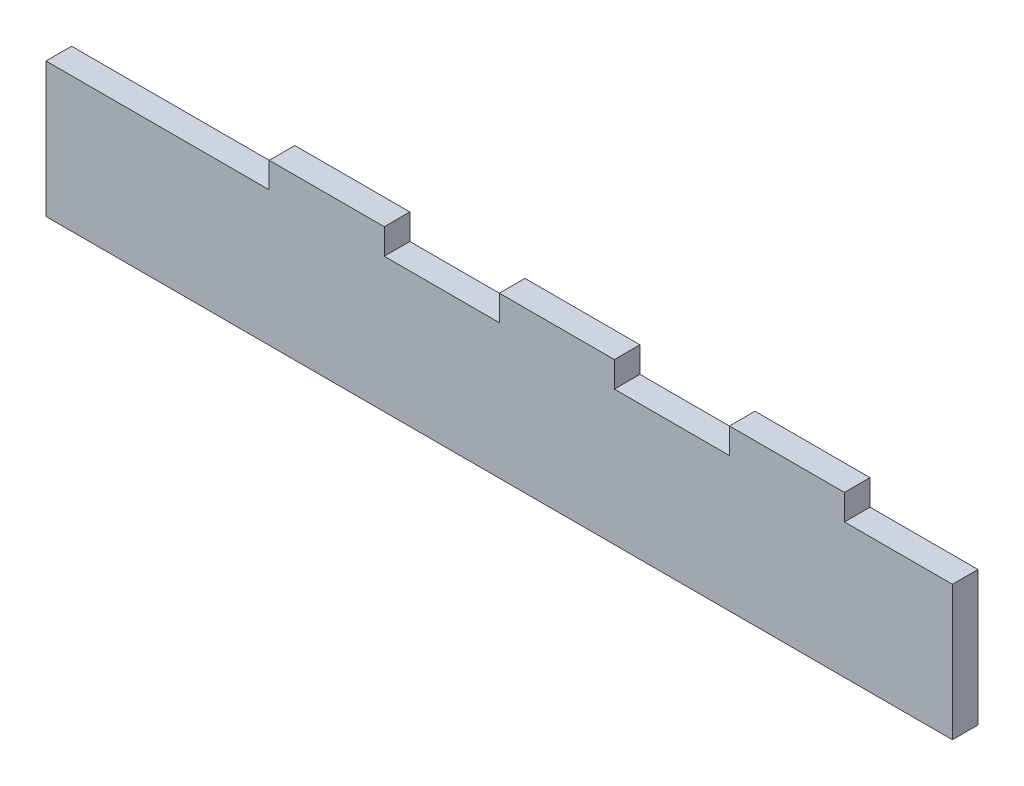
SolidWorks part; units mm, degrees
ref_plane "Front Plane" through (0, 0, 0) normal (0, 0, 1) x (1, 0, 0)
ref_plane "Top Plane" through (0, 0, 0) normal (0, 1, 0) x (1, 0, 0)
ref_plane "Right Plane" through (0, 0, 0) normal (1, 0, 0) x (0, 0, -1)
sketch "Sketch1" plane through (0, 0, 0) normal (0, 0, 1) x (1, 0, 0)
  line L1 (0, 0) -> (170.942, 0)
  line L2 (0, 0) -> (0, 30.226)
  line L3 (0, 30.226) -> (170.942, 30.226)
  line L4 (170.942, 0) -> (170.942, 30.226)
  dimension "D1" = 170.942
  dimension "D2" = 30.226
extrude "Boss-Extrude1" add sketch "Sketch1" along normal blind 4.826
sketch "Sketch2" plane through (0, 0, 0) normal (0, 0, -1) x (-1, 0, 0)
  line L0 (0, 25.4) -> (-42.0951, 25.4) construction
  line L1 (0, 25.4) -> (0, 30.226) construction
  line L2 (0, 30.226) -> (-42.0951, 30.226) construction
  line L3 (-42.0951, 30.226) -> (-42.0951, 25.4) construction
  line L4 (-63.7923, 25.4) -> (-85.4895, 25.4) construction
  line L5 (-85.4895, 30.226) -> (-85.4895, 25.4) construction
  line L6 (-63.7923, 30.226) -> (-63.7923, 25.4) construction
  line L7 (-63.7923, 30.226) -> (-85.4895, 30.226) construction
  line L8 (-107.1867, 25.4) -> (-128.8839, 25.4) construction
  line L9 (-128.8839, 30.226) -> (-128.8839, 25.4) construction
  line L10 (-107.1867, 30.226) -> (-107.1867, 25.4) construction
  line L11 (-107.1867, 30.226) -> (-128.8839, 30.226) construction
  line L12 (-150.5811, 25.4) -> (-170.979, 25.4) construction
  line L13 (-150.5811, 30.226) -> (-150.5811, 25.4) construction
  line L14 (-170.979, 25.4) -> (-170.979, 30.226) construction
  line L15 (-150.5811, 30.226) -> (-170.979, 30.226) construction
  line L16 (0, 25.4) -> (-42.0951, 25.4)
  line L17 (0, 25.4) -> (0, 30.226)
  line L18 (0, 30.226) -> (-42.0951, 30.226)
  line L19 (-42.0951, 30.226) -> (-42.0951, 25.4)
  line L20 (-63.7923, 25.4) -> (-85.4895, 25.4)
  line L21 (-85.4895, 30.226) -> (-85.4895, 25.4)
  line L22 (-63.7923, 30.226) -> (-63.7923, 25.4)
  line L23 (-63.7923, 30.226) -> (-85.4895, 30.226)
  line L24 (-107.1867, 25.4) -> (-128.8839, 25.4)
  line L25 (-128.8839, 30.226) -> (-128.8839, 25.4)
  line L26 (-107.1867, 30.226) -> (-107.1867, 25.4)
  line L27 (-107.1867, 30.226) -> (-128.8839, 30.226)
  line L28 (-150.5811, 25.4) -> (-170.979, 25.4)
  line L29 (-150.5811, 30.226) -> (-150.5811, 25.4)
  line L30 (-170.979, 25.4) -> (-170.979, 30.226)
  line L31 (-150.5811, 30.226) -> (-170.979, 30.226)
extrude "Cut-Extrude1" cut sketch "Sketch2" against normal through all
equation "\"MDF\"= 0.19in"
equation "\"PVCID\" = 2.067in"
equation "\"PVCOD\" = 2.375in"
equation "\"GenDiameter\"= 60mm"
equation "\"GenCutDiameter\" = 1.8in"
equation "\"GenCutDistance\" = 1"
equation "\"TowerHeight\" = 6in"
equation "\"TowerFrontBase\" = 3in"
equation "\"FunnelHeight\" = 1in"
equation "\"FunnelAngle\" = 20"
equation "\"TowerSideBase\" = 3in"
equation "\"TowerPanelLength\" = 2in"
equation "\"TowerPanelLeeway\" = 0.5in"
equation "\"BaseLength\" = 9in"
equation "\"BaseWidth\" = 10in"
equation "\"WheelHoleLength\" = 3.25in"
equation "\"WheelHoleWidth\" = 26mm"
equation "\"WheelHoleFromBack\" = 1.5in"
equation "\"DropLength\" = 1in"
equation "\"DropWidth\" = 8.5in"
equation "\"BumperWidth\" = 1in"
equation "\"SmallHexDiameter\" = 0.185in"
equation "\"SmallHexHeight\" = 0.701in"
equation "\"ScrewSize\" = 0.106in"
equation "\"BigHexDiameter\" = 0.251in"
equation "\"BigHexHeight\" = 0.374in"
equation "\"PCBThickness\" = 0.066in"
equation "\"ConnectorHeight\" = 0.517in"
equation "\"BoardHeight\" = 0.583in"
equation "\"UnoStackHeight\" = 1.351in"
equation "\"UnoStackWidth\" = 3.053in"
equation "\"UnoStackLength\" = 3.152in"
equation "\"HBridgeWidth\" = 1.797in"
equation "\"HBridgeLength\" = 2.236in"
equation "\"DSWidth\" = 1.820in"
equation "\"DSLength\" = 1.833in"
equation "\"StepperWidth\" = 1.799in"
equation "\"StepperLength\" = 2.248in"
equation "\"ULNWidth\" = 1.304in"
equation "\"ULNLength\" = 1.545in"
equation "\"VSwitchHeight\" = 0.392in"
equation "\"VSwitchWidth\" = 0.637in"
equation "\"VSwitchLength\" = 1.097in"
equation "\"SkateWheelDiameter\" = 80mm"
equation "\"SkateWheelThickness\" = 24mm"
equation "\"BaseDistance\" = 3in"
equation "\"DummyVar\" = 2in"
equation "\"D2@Sketch1\"=\"MDF\"+1in"
equation "\"D1@Boss-Extrude1\"=\"MDF\""
